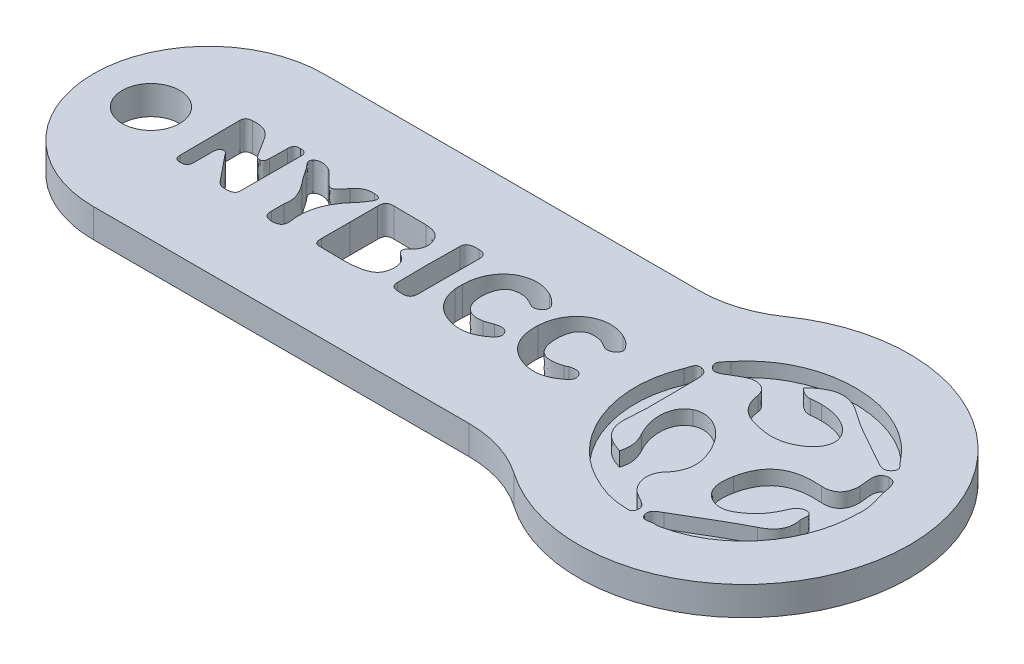
SolidWorks part; units mm, degrees
ref_plane "Plan de face" through (0, 0, 0) normal (0, 0, 1) x (1, 0, 0)
ref_plane "Plan de dessus" through (0, 0, 0) normal (0, 1, 0) x (1, 0, 0)
ref_plane "Plan de droite" through (0, 0, 0) normal (1, 0, 0) x (0, 0, -1)
sketch "Esquisse1" plane through (0, 0, 0) normal (0, 1, 0) x (1, 0, 0)
  line L0 (-14.5, 0) -> (0, 0) construction
  line L1 (-18.5, 8) -> (18.5, 8)
  line L2 (-18.5, 8) -> (-18.5, -8)
  line L3 (-18.5, -8) -> (18.5, -8)
  line L5 (-18.5, 8) -> (18.5, -8) construction
  line L6 (-18.5, -8) -> (18.5, 8) construction
  arc A0 (18.5, -8) -> (18.5, 8) centre (26.7614, 0) ccw
  circle A1 centre (-14.5, 0) radius 2
  point P0 (0, 0)
  dimension "D3" = 23
  dimension "D5" = 4
  dimension "D1" = 37
  dimension "D2" = 16
  dimension "D4" = 4
extrude "Boss.-Extru.1" add sketch "Esquisse1" along normal blind 2
sketch "Esquisse2" plane through (0, 2, 0) normal (0, 1, 0) x (1, 0, 0)
  line L0 (20.6551, -5.913) -> (-11.0872, -5.913)
  line L1 (-11.0872, -5.913) -> (-11.0872, 5.913)
  line L2 (-11.0872, 5.913) -> (20.6551, 5.913)
  line L3 (20.6551, 5.913) -> (20.5787, 5.7726)
  line L7 (18.5, 8) -> (-18.5, 8)
  line L8 (-18.5, 8) -> (-18.5, -8)
  line L9 (-18.5, -8) -> (18.5, -8)
  line L10 (18.5, 8) -> (-18.5, 8)
  line L11 (-18.5, 8) -> (-18.5, -8)
  line L12 (-18.5, -8) -> (18.5, -8)
  arc A2 (20.6551, -5.913) -> (20.6551, 5.913) centre (26.7614, 0) ccw
  arc A3 (20.6551, -5.913) -> (20.6551, 5.913) centre (26.7614, 0) ccw
  arc A4 (18.5, -8) -> (18.5, 8) centre (26.7614, 0) ccw
  arc A5 (18.5, -8) -> (18.5, 8) centre (26.7614, 0) ccw
  spline S0 degree 3 poles (-0.6478, -2.0038) (-0.6441, -1.3402) (-0.6453, -0.6767) (-0.6445, -0.0131) knots 10 10 10 10 11 11 11 11
  spline S1 degree 3 poles (-0.2444, -2.5319) (-0.5915, -2.5436) (-0.6494, -2.2881) (-0.6478, -2.0038) knots 9 9 9 9 10 10 10 10
  spline S2 degree 3 poles (2.6339, -2.4261) (1.6814, -2.6501) (0.7151, -2.4999) (-0.2444, -2.5319) knots 8 8 8 8 9 9 9 9
  spline S3 degree 3 poles (3.5955, -1.6042) (3.4795, -2.1073) (3.0976, -2.3172) (2.6339, -2.4261) knots 7 7 7 7 8 8 8 8
  spline S4 degree 3 poles (3.1404, -0.2543) (3.6591, -0.5766) (3.7194, -1.067) (3.5955, -1.6042) knots 6 6 6 6 7 7 7 7
  spline S5 degree 3 poles (3.0614, 0.4466) (2.7421, 0.169) (2.8091, -0.0484) (3.1404, -0.2543) knots 5 5 5 5 6 6 6 6
  spline S6 degree 3 poles (3.3667, 1.7784) (3.5818, 1.2681) (3.4841, 0.8142) (3.0614, 0.4466) knots 4 4 4 4 5 5 5 5
  spline S7 degree 3 poles (2.1595, 2.4683) (2.6617, 2.4468) (3.1433, 2.3081) (3.3667, 1.7784) knots 3 3 3 3 4 4 4 4
  spline S8 degree 3 poles (-0.0875, 2.4853) (0.6611, 2.4633) (1.4117, 2.5002) (2.1595, 2.4683) knots 2 2 2 2 3 3 3 3
  spline S9 degree 3 poles (-0.6469, 1.9131) (-0.6578, 2.3192) (-0.5122, 2.4979) (-0.0875, 2.4853) knots 1 1 1 1 2 2 2 2
  spline S10 degree 3 poles (-0.6445, -0.0131) (-0.6437, 0.629) (-0.6298, 1.2714) (-0.6469, 1.9131) knots 0 0 0 0 1 1 1 1
  spline S11 degree 3 poles (-6.326, 2.2344) (-6.3313, 1.5279) (-6.3292, 0.8215) (-6.3298, 0.115) knots 18 18 18 18 19 19 19 19
  spline S12 degree 3 poles (-6.7937, 2.7014) (-6.4734, 2.6981) (-6.3236, 2.5559) (-6.326, 2.2344) knots 17 17 17 17 18 18 18 18
  spline S13 degree 3 poles (-7.2477, 2.2297) (-7.2527, 2.5492) (-7.1247, 2.7049) (-6.7937, 2.7014) knots 16 16 16 16 17 17 17 17
  spline S14 degree 3 poles (-7.2678, 1.0107) (-7.2422, 1.4159) (-7.2415, 1.8234) (-7.2477, 2.2297) knots 15 15 15 15 16 16 16 16
  spline S15 degree 3 poles (-7.5105, 0.6021) (-7.2992, 0.6429) (-7.278, 0.8514) (-7.2678, 1.0107) knots 14 14 14 14 15 15 15 15
  spline S16 degree 3 poles (-7.9101, 0.8663) (-7.8168, 0.7208) (-7.7099, 0.5635) (-7.5105, 0.6021) knots 13 13 13 13 14 14 14 14
  spline S17 degree 3 poles (-8.6262, 2.0024) (-8.398, 1.6174) (-8.1518, 1.2431) (-7.9101, 0.8663) knots 12 12 12 12 13 13 13 13
  spline S18 degree 3 poles (-10.1531, 2.7061) (-9.5006, 2.7681) (-8.9761, 2.5926) (-8.6262, 2.0024) knots 11 11 11 11 12 12 12 12
  spline S19 degree 3 poles (-10.6046, 2.2872) (-10.5907, 2.573) (-10.4437, 2.6929) (-10.1531, 2.7061) knots 10 10 10 10 11 11 11 11
  spline S20 degree 3 poles (-10.5829, -1.8867) (-10.591, -0.4954) (-10.5979, 0.8959) (-10.6046, 2.2872) knots 9 9 9 9 10 10 10 10
  spline S21 degree 3 poles (-10.1559, -2.3223) (-10.4501, -2.3155) (-10.5895, -2.1754) (-10.5829, -1.8867) knots 8 8 8 8 9 9 9 9
  spline S22 degree 3 poles (-9.6607, -1.8867) (-9.6658, -2.2196) (-9.8476, -2.3294) (-10.1559, -2.3223) knots 7 7 7 7 8 8 8 8
  spline S23 degree 3 poles (-9.6574, -0.6023) (-9.6581, -1.0305) (-9.6639, -1.4586) (-9.6607, -1.8867) knots 6 6 6 6 7 7 7 7
  spline S24 degree 3 poles (-9.4396, -0.1044) (-9.6359, -0.1895) (-9.657, -0.4031) (-9.6574, -0.6023) knots 5 5 5 5 6 6 6 6
  spline S25 degree 3 poles (-8.9907, -0.371) (-9.1068, -0.2291) (-9.2067, -0.0034) (-9.4396, -0.1044) knots 4 4 4 4 5 5 5 5
  spline S26 degree 3 poles (-7.6174, -2.066) (-8.071, -1.4976) (-8.5298, -0.9334) (-8.9907, -0.371) knots 3 3 3 3 4 4 4 4
  spline S27 degree 3 poles (-6.6227, -2.3125) (-6.978, -2.3961) (-7.3461, -2.4059) (-7.6174, -2.066) knots 2 2 2 2 3 3 3 3
  spline S28 degree 3 poles (-6.3332, -1.619) (-6.3358, -1.8884) (-6.2546, -2.2259) (-6.6227, -2.3125) knots 1 1 1 1 2 2 2 2
  spline S29 degree 3 poles (-6.3298, 0.115) (-6.3304, -0.463) (-6.3278, -1.041) (-6.3332, -1.619) knots 0 0 0 0 1 1 1 1
  spline S30 degree 3 poles (15.134, 1.5867) (14.1247, 1.8204) (13.5732, 1.3125) (13.5613, 0.1569) knots 11 11 11 11 12 12 12 12
  spline S31 degree 3 poles (15.6468, 1.3409) (15.4848, 1.4388) (15.3146, 1.5449) (15.134, 1.5867) knots 10 10 10 10 11 11 11 11
  spline S32 degree 3 poles (16.5098, 1.4875) (16.2919, 1.2335) (15.9824, 1.138) (15.6468, 1.3409) knots 9 9 9 9 10 10 10 10
  spline S33 degree 3 poles (16.3221, 2.2066) (16.5147, 2.0011) (16.7459, 1.7626) (16.5098, 1.4875) knots 8 8 8 8 9 9 9 9
  spline S34 degree 3 poles (15.6943, 2.6388) (15.9312, 2.5316) (16.1453, 2.3955) (16.3221, 2.2066) knots 7 7 7 7 8 8 8 8
  spline S35 degree 3 poles (12.1198, 0.2826) (12.2175, 2.2847) (13.9775, 3.4157) (15.6943, 2.6388) knots 6 6 6 6 7 7 7 7
  spline S36 degree 3 poles (13.463, -2.2907) (12.4307, -1.7591) (12.0672, -0.7993) (12.1198, 0.2826) knots 5 5 5 5 6 6 6 6
  spline S37 degree 3 poles (16.1783, -2.0982) (15.3182, -2.723) (14.3882, -2.7673) (13.463, -2.2907) knots 4 4 4 4 5 5 5 5
  spline S38 degree 3 poles (16.5422, -1.3117) (16.7435, -1.6759) (16.4351, -1.9116) (16.1783, -2.0982) knots 3 3 3 3 4 4 4 4
  spline S39 degree 3 poles (15.6862, -1.1133) (16.0121, -1.0073) (16.3614, -0.9848) (16.5422, -1.3117) knots 2 2 2 2 3 3 3 3
  spline S40 degree 3 poles (15.4506, -1.2123) (15.5311, -1.1849) (15.6054, -1.1395) (15.6862, -1.1133) knots 1 1 1 1 2 2 2 2
  spline S41 degree 3 poles (13.5613, 0.1569) (13.5475, -1.1495) (14.2151, -1.6336) (15.4506, -1.2123) knots 0 0 0 0 1 1 1 1
  spline S42 degree 3 poles (7.034, -0.3815) (7.0099, -0.2138) (7.031, -0.0396) (7.0312, 0.1316) knots 13 13 13 13 14 14 14 14
  spline S43 degree 3 poles (8.5112, -2.4007) (7.6222, -2.0382) (7.1681, -1.3141) (7.034, -0.3815) knots 12 12 12 12 13 13 13 13
  spline S44 degree 3 poles (11.06, -2.1085) (10.272, -2.7073) (9.3984, -2.7625) (8.5112, -2.4007) knots 11 11 11 11 12 12 12 12
  spline S45 degree 3 poles (11.3988, -1.3117) (11.6114, -1.6699) (11.317, -1.9133) (11.06, -2.1085) knots 10 10 10 10 11 11 11 11
  spline S46 degree 3 poles (10.5288, -1.1382) (10.8494, -1.041) (11.2051, -0.9855) (11.3988, -1.3117) knots 9 9 9 9 10 10 10 10
  spline S47 degree 3 poles (9.9235, -1.34) (10.1303, -1.2982) (10.3252, -1.1999) (10.5288, -1.1382) knots 8 8 8 8 9 9 9 9
  spline S48 degree 3 poles (8.5188, -0.6533) (8.7101, -1.2108) (9.2409, -1.4781) (9.9235, -1.34) knots 7 7 7 7 8 8 8 8
  spline S49 degree 3 poles (9.0314, 1.5012) (8.4752, 1.2287) (8.2314, 0.1846) (8.5188, -0.6533) knots 6 6 6 6 7 7 7 7
  spline S50 degree 3 poles (9.4007, 1.5885) (9.2759, 1.5669) (9.1423, 1.5555) (9.0314, 1.5012) knots 5 5 5 5 6 6 6 6
  spline S51 degree 3 poles (10.6171, 1.2922) (10.2401, 1.5152) (9.8484, 1.6661) (9.4007, 1.5885) knots 4 4 4 4 5 5 5 5
  spline S52 degree 3 poles (11.3616, 1.4608) (11.1665, 1.251) (10.9118, 1.1179) (10.6171, 1.2922) knots 3 3 3 3 4 4 4 4
  spline S53 degree 3 poles (11.2404, 2.1354) (11.4173, 1.9545) (11.5948, 1.7118) (11.3616, 1.4608) knots 2 2 2 2 3 3 3 3
  spline S54 degree 3 poles (10.627, 2.5891) (10.8519, 2.4763) (11.0644, 2.3153) (11.2404, 2.1354) knots 1 1 1 1 2 2 2 2
  spline S55 degree 3 poles (7.0312, 0.1316) (7.017, 2.2181) (8.8598, 3.4766) (10.627, 2.5891) knots 0 0 0 0 1 1 1 1
  spline S56 degree 3 poles (20.8247, -2.0529) (20.69, -3.4272) (21.2917, -4.0532) (22.4958, -4.411) knots 13 13 13 13 14 14 14 14
  spline S57 degree 3 poles (20.8707, 2.5877) (20.8518, 1.04) (20.975, -0.5195) (20.8247, -2.0529) knots 12 12 12 12 13 13 13 13
  spline S58 degree 3 poles (20.3589, 3.4373) (20.7757, 3.356) (20.8759, 3.0031) (20.8707, 2.5877) knots 11 11 11 11 12 12 12 12
  spline S59 degree 3 poles (19.7877, 2.7925) (19.904, 3.0638) (19.9018, 3.5264) (20.3589, 3.4373) knots 10 10 10 10 11 11 11 11
  spline S60 degree 3 poles (23.1867, -6.7698) (19.8096, -4.9332) (18.3001, -0.6793) (19.7877, 2.7925) knots 9 9 9 9 10 10 10 10
  spline S61 degree 3 poles (25.9567, -7.6289) (24.9549, -7.6033) (24.0484, -7.2383) (23.1867, -6.7698) knots 8 8 8 8 9 9 9 9
  spline S62 degree 3 poles (26.6612, -7.3752) (26.5599, -7.7864) (26.214, -7.6353) (25.9567, -7.6289) knots 7 7 7 7 8 8 8 8
  spline S63 degree 3 poles (26.268, -6.6952) (26.5299, -6.8467) (26.7435, -7.0408) (26.6612, -7.3752) knots 6 6 6 6 7 7 7 7
  spline S64 degree 3 poles (25.7401, -6.3888) (25.9117, -6.4978) (26.0918, -6.5935) (26.268, -6.6952) knots 5 5 5 5 6 6 6 6
  spline S65 degree 3 poles (25.3508, -4.1307) (24.7364, -4.8112) (24.986, -5.9092) (25.7401, -6.3888) knots 4 4 4 4 5 5 5 5
  spline S66 degree 3 poles (25.5618, -1.0872) (26.0741, -2.135) (26.252, -3.1326) (25.3508, -4.1307) knots 3 3 3 3 4 4 4 4
  spline S67 degree 3 poles (22.5765, 0.6204) (23.5077, 1.0885) (24.8768, 0.3142) (25.5618, -1.0872) knots 2 2 2 2 3 3 3 3
  spline S68 degree 3 poles (22.2705, -2.6617) (21.4852, -1.2334) (21.6533, 0.1562) (22.5765, 0.6204) knots 1 1 1 1 2 2 2 2
  spline S69 degree 3 poles (22.4958, -4.411) (22.6895, -3.7654) (22.5874, -3.2375) (22.2705, -2.6617) knots 0 0 0 0 1 1 1 1
  spline S70 degree 3 poles (34.2908, 1.9196) (34.5116, 1.2692) (34.6572, 0.5833) (34.5723, 0.043) knots 15 15 15 15 16 16 16 16
  spline S71 degree 3 poles (33.4768, 3.345) (34.1825, 3.4033) (34.1107, 2.4507) (34.2908, 1.9196) knots 14 14 14 14 15 15 15 15
  spline S72 degree 3 poles (32.9899, 1.8117) (32.9782, 2.3605) (32.6504, 3.2769) (33.4768, 3.345) knots 13 13 13 13 14 14 14 14
  spline S73 degree 3 poles (31.6503, 0.4778) (32.418, 0.4191) (33.0107, 0.8361) (32.9899, 1.8117) knots 12 12 12 12 13 13 13 13
  spline S74 degree 3 poles (28.0087, -2.0014) (28.3864, -0.1074) (29.5871, 0.6354) (31.6503, 0.4778) knots 11 11 11 11 12 12 12 12
  spline S75 degree 3 poles (28.7232, -4.1459) (27.8705, -3.6814) (27.8418, -2.8385) (28.0087, -2.0014) knots 10 10 10 10 11 11 11 11
  spline S76 degree 3 poles (30.8285, -3.6402) (30.2151, -4.1482) (29.5238, -4.582) (28.7232, -4.1459) knots 9 9 9 9 10 10 10 10
  spline S77 degree 3 poles (31.9149, -2.0477) (31.6643, -2.6604) (31.3386, -3.2179) (30.8285, -3.6402) knots 8 8 8 8 9 9 9 9
  spline S78 degree 3 poles (32.6672, -1.5283) (32.3502, -1.494) (32.0434, -1.7332) (31.9149, -2.0477) knots 7 7 7 7 8 8 8 8
  spline S79 degree 3 poles (32.9603, -2.3153) (32.9084, -2.0339) (33.1548, -1.5813) (32.6672, -1.5283) knots 6 6 6 6 7 7 7 7
  spline S80 degree 3 poles (31.9014, -4.2266) (32.7588, -3.7947) (33.1312, -3.2385) (32.9603, -2.3153) knots 5 5 5 5 6 6 6 6
  spline S81 degree 3 poles (27.7784, -6.5813) (29.1518, -5.7938) (30.49, -4.9378) (31.9014, -4.2266) knots 4 4 4 4 5 5 5 5
  spline S82 degree 3 poles (27.221, -7.3854) (27.066, -6.9234) (27.4568, -6.7657) (27.7784, -6.5813) knots 3 3 3 3 4 4 4 4
  spline S83 degree 3 poles (28.1667, -7.6063) (27.8477, -7.5375) (27.3951, -7.903) (27.221, -7.3854) knots 2 2 2 2 3 3 3 3
  spline S84 degree 3 poles (28.5281, -7.569) (28.4093, -7.5932) (28.2794, -7.6307) (28.1667, -7.6063) knots 1 1 1 1 2 2 2 2
  spline S85 degree 3 poles (34.5723, 0.043) (34.5572, -3.6847) (31.9805, -6.8615) (28.5281, -7.569) knots 0 0 0 0 1 1 1 1
  spline S86 degree 3 poles (-4.0375, -2.0941) (-4.0389, -1.837) (-4.0371, -1.5798) (-4.0366, -1.1939) knots 12 12 12 12 13 13 13 13
  spline S87 degree 3 poles (-3.4486, -2.6866) (-3.8547, -2.6721) (-4.0351, -2.4835) (-4.0375, -2.0941) knots 11 11 11 11 12 12 12 12
  spline S88 degree 3 poles (-2.7742, -2.0038) (-2.7002, -2.4967) (-2.9519, -2.7045) (-3.4486, -2.6866) knots 10 10 10 10 11 11 11 11
  spline S89 degree 3 poles (-1.6158, 1.3812) (-2.4983, 0.4205) (-2.9748, -0.6693) (-2.7742, -2.0038) knots 9 9 9 9 10 10 10 10
  spline S90 degree 3 poles (-1.2023, 1.9516) (-1.3309, 1.7551) (-1.4579, 1.5531) (-1.6158, 1.3812) knots 8 8 8 8 9 9 9 9
  spline S91 degree 3 poles (-1.5107, 2.5549) (-1.0074, 2.5231) (-0.9576, 2.3253) (-1.2023, 1.9516) knots 7 7 7 7 8 8 8 8
  spline S92 degree 3 poles (-2.6553, 2.0123) (-2.3469, 2.4021) (-2.0134, 2.5867) (-1.5107, 2.5549) knots 6 6 6 6 7 7 7 7
  spline S93 degree 3 poles (-4.0605, 1.947) (-3.3405, 1.182) (-3.3258, 1.1647) (-2.6553, 2.0123) knots 5 5 5 5 6 6 6 6
  spline S94 degree 3 poles (-4.6349, 2.4518) (-4.4141, 2.3416) (-4.2354, 2.1329) (-4.0605, 1.947) knots 4 4 4 4 5 5 5 5
  spline S95 degree 3 poles (-5.6628, 2.4363) (-5.4111, 2.6916) (-4.9649, 2.6164) (-4.6349, 2.4518) knots 3 3 3 3 4 4 4 4
  spline S96 degree 3 poles (-5.3839, 1.679) (-5.5353, 1.9141) (-5.9259, 2.1694) (-5.6628, 2.4363) knots 2 2 2 2 3 3 3 3
  spline S97 degree 3 poles (-4.6793, 0.6846) (-4.935, 0.9994) (-5.164, 1.3377) (-5.3839, 1.679) knots 1 1 1 1 2 2 2 2
  spline S98 degree 3 poles (-4.0366, -1.1939) (-3.8891, -0.5375) (-4.2008, 0.0951) (-4.6793, 0.6846) knots 0 0 0 0 1 1 1 1
  spline S99 degree 3 poles (28.4489, 6.1036) (27.188, 7.04) (26.1934, 6.8331) (25.1006, 5.7726) knots 13 13 13 13 14 14 14 14
  spline S100 degree 3 poles (32.2257, 3.8741) (30.9697, 4.6247) (29.6158, 5.2371) (28.4489, 6.1036) knots 12 12 12 12 13 13 13 13
  spline S101 degree 3 poles (33.1947, 3.8749) (32.8996, 3.5244) (32.5762, 3.6646) (32.2257, 3.8741) knots 11 11 11 11 12 12 12 12
  spline S102 degree 3 poles (32.9181, 4.6879) (33.0852, 4.4632) (33.51, 4.2491) (33.1947, 3.8749) knots 10 10 10 10 11 11 11 11
  spline S103 degree 3 poles (21.0052, 4.8289) (23.9283, 8.5635) (30.0923, 8.4884) (32.9181, 4.6879) knots 9 9 9 9 10 10 10 10
  spline S104 degree 3 poles (20.6512, 3.9116) (20.3706, 4.3111) (20.8091, 4.5784) (21.0052, 4.8289) knots 8 8 8 8 9 9 9 9
  spline S105 degree 3 poles (21.7112, 3.951) (21.3602, 3.7373) (20.9758, 3.4496) (20.6512, 3.9116) knots 7 7 7 7 8 8 8 8
  spline S106 degree 3 poles (22.4531, 4.3729) (22.1989, 4.2458) (21.9541, 4.099) (21.7112, 3.951) knots 6 6 6 6 7 7 7 7
  spline S107 degree 3 poles (23.9755, 3.7431) (23.8907, 4.348) (23.204, 4.7486) (22.4531, 4.3729) knots 5 5 5 5 6 6 6 6
  spline S108 degree 3 poles (26.5035, 1.7576) (25.3358, 1.9291) (24.1957, 2.1695) (23.9755, 3.7431) knots 4 4 4 4 5 5 5 5
  spline S109 degree 3 poles (29.457, 3.5205) (29.4094, 2.5046) (27.9199, 1.5498) (26.5035, 1.7576) knots 3 3 3 3 4 4 4 4
  spline S110 degree 3 poles (26.7445, 5.4024) (28.3033, 5.391) (29.5054, 4.5538) (29.457, 3.5205) knots 2 2 2 2 3 3 3 3
  spline S111 degree 3 poles (26.0136, 5.3603) (26.2569, 5.3802) (26.5009, 5.4042) (26.7445, 5.4024) knots 1 1 1 1 2 2 2 2
  spline S112 degree 3 poles (25.1006, 5.7726) (25.3972, 5.4799) (25.6664, 5.3319) (26.0136, 5.3603) knots 0 0 0 0 1 1 1 1
  spline S113 degree 3 poles (6.0618, 2.2443) (6.0551, 1.5401) (6.0584, 0.8358) (6.0578, 0.1316) knots 6 6 6 6 7 7 7 7
  spline S114 degree 3 poles (5.4775, 2.8223) (5.8787, 2.8327) (6.0656, 2.6459) (6.0618, 2.2443) knots 5 5 5 5 6 6 6 6
  spline S115 degree 3 poles (4.644, 2.3472) (4.6569, 2.8368) (5.1086, 2.8127) (5.4775, 2.8223) knots 4 4 4 4 5 5 5 5
  spline S116 degree 3 poles (4.6408, -2.0038) (4.607, -0.5541) (4.6057, 0.8976) (4.644, 2.3472) knots 3 3 3 3 4 4 4 4
  spline S117 degree 3 poles (5.5027, -2.5204) (5.0987, -2.5151) (4.653, -2.5272) (4.6408, -2.0038) knots 2 2 2 2 3 3 3 3
  spline S118 degree 3 poles (6.0561, -1.9172) (6.0567, -2.2902) (5.9381, -2.526) (5.5027, -2.5204) knots 1 1 1 1 2 2 2 2
  spline S119 degree 3 poles (6.0578, 0.1316) (6.0573, -0.5513) (6.055, -1.2343) (6.0561, -1.9172) knots 0 0 0 0 1 1 1 1
  dimension "D1" = 3
  dimension "D2" = 0
sketch "Esquisse3" plane through (0, 2, 0) normal (0, 1, 0) x (1, 0, 0)
  line L0 (-18.5, -8) -> (18.5, -8) construction
  line L1 (18.5, 8) -> (-18.5, 8) construction
  line L2 (-18.5, 8) -> (-18.5, -8) construction
  line L3 (-18.5, -8) -> (18.5, -8)
  line L4 (18.5, 8) -> (-18.5, 8)
  line L5 (-18.5, 8) -> (-18.5, -8)
  line L6 (20.6551, -5.913) -> (-11.0872, -5.913) construction
  line L7 (-11.0872, -5.913) -> (-11.0872, 5.913) construction
  line L8 (-11.0872, 5.913) -> (20.6551, 5.913) construction
  line L9 (20.6551, -5.913) -> (-11.0872, -5.913)
  line L10 (-11.0872, -5.913) -> (-11.0872, 5.913)
  line L11 (-11.0872, 5.913) -> (20.6551, 5.913)
  arc A0 (18.5, -8) -> (18.5, 8) centre (26.7614, 0) ccw construction
  arc A1 (18.5, -8) -> (18.5, 8) centre (26.7614, 0) ccw
  arc A2 (20.6551, -5.913) -> (20.6551, 5.913) centre (26.7614, 0) ccw construction
  arc A3 (20.6551, -5.913) -> (20.6551, 5.913) centre (26.7614, 0) ccw
  circle A4 centre (-14.5, 0) radius 2 construction
  circle A5 centre (-14.5, 0) radius 2
sketch "Esquisse4" plane through (0, 2, 0) normal (0, 1, 0) x (1, 0, 0)
  line L0 (20.6551, 5.913) -> (20.5787, 5.7726) construction
  line L7 (20.6551, 5.913) -> (20.5787, 5.7726)
  spline S0 degree 3 poles (-988.6364, -156.5278) (987.1828, 15.4399) (-988.3584, -17.0259) (987.0045, 156.5819) knots -42.156378 -42.156378 -42.156378 -42.156378 63.578843 63.578843 63.578843 63.578843 only from (-0.6478, -2.0038) to (-0.6445, -0.0131) construction
  spline S1 degree 3 poles (998.9683, -27.814) (-1000.7869, -43.7538) (999.5085, 44.8287) (-1000.2647, 29.0633) knots -28.01613 -28.01613 -28.01613 -28.01613 28.610346 28.610346 28.610346 28.610346 only from (-0.6445, -0.0131) to (-0.6469, 1.9131) construction
  spline S2 degree 3 poles (-806.3377, -590.4224) (881.935, 349.9228) (-947.6891, -158.8633) (999.6546, 24.973) knots -19.095692 -19.095692 -19.095692 -19.095692 19.93203 19.93203 19.93203 19.93203 only from (-0.6469, 1.9131) to (-0.0875, 2.4853) construction
  spline S3 degree 3 poles (-5.6723, 1002.4697) (-52.037, -997.9234) (54.0549, 1002.8855) (7.2197, -997.5168) knots -17.384502 -17.384502 -17.384502 -17.384502 22.307886 22.307886 22.307886 22.307886 only from (-0.0875, 2.4853) to (2.1595, 2.4683) construction
  spline S4 degree 3 poles (673.4526, 743.6589) (-679.078, -755.5216) (663.7455, 775.9327) (-613.6237, -785.1772) knots -11.375763 -11.375763 -11.375763 -11.375763 16.803532 16.803532 16.803532 16.803532 only from (2.1595, 2.4683) to (3.3667, 1.7784) construction
  spline S5 degree 3 poles (-587.2716, -805.1573) (-148.2054, 805.2207) (588.7087, -710.7698) (-808.9164, 584.1264) knots -28.547334 -28.547334 -28.547334 -28.547334 29.703561 29.703561 29.703561 29.703561 only from (3.3667, 1.7784) to (3.0614, 0.4466) construction
  spline S6 degree 3 poles (954.8081, 307.3287) (-985.562, -347.9861) (973.0885, 409.0271) (-860.9773, -503.5381) knots -12.018303 -12.018303 -12.018303 -12.018303 27.813032 27.813032 27.813032 27.813032 only from (3.0614, 0.4466) to (3.1404, -0.2543) construction
  spline S7 degree 3 poles (-925.837, -370.3897) (942.0359, 411.4876) (-930.5378, -430.2075) (917.0272, 405.3868) knots -7.406116 -7.406116 -7.406116 -7.406116 22.66661 22.66661 22.66661 22.66661 only from (3.1404, -0.2543) to (3.5955, -1.6042) construction
  spline S8 degree 3 poles (-670.3816, 737.1466) (709.5487, -735.2893) (-709.848, 726.7854) (686.6085, -731.9215) knots -7.128626 -7.128626 -7.128626 -7.128626 24.107352 24.107352 24.107352 24.107352 only from (3.5955, -1.6042) to (2.6339, -2.4261) construction
  spline S9 degree 3 poles (-1.3954, 997.5644) (49.6027, -1003.949) (-48.2188, 998.8305) (2.8476, -1002.5252) knots -3.490216 -3.490216 -3.490216 -3.490216 20.834721 20.834721 20.834721 20.834721 only from (2.6339, -2.4261) to (-0.2444, -2.5319) construction
  spline S10 degree 3 poles (709.1918, 702.2371) (-704.6122, -729.3467) (696.5433, 732.4618) (-690.1218, -726.3134) knots -4.311026 -4.311026 -4.311026 -4.311026 24.68846 24.68846 24.68846 24.68846 only from (-0.2444, -2.5319) to (-0.6478, -2.0038) construction
  spline S11 degree 3 poles (77.2752, -996.4806) (274.7762, 726.1333) (-598.1401, -348.7164) (1002.8087, -146.0471) knots -5.22656 -5.22656 -5.22656 -5.22656 29.924053 29.924053 29.924053 29.924053 only from (15.134, 1.5867) to (13.5613, 0.1569) construction
  spline S12 degree 3 poles (951.6619, 346.5188) (-635.4613, 133.2102) (336.241, -584.3672) (57.8715, 997.8829) knots -15.670122 -15.670122 -15.670122 -15.670122 16.612834 16.612834 16.612834 16.612834 only from (13.5613, 0.1569) to (15.4506, -1.2123) construction
  spline S13 degree 3 poles (-312.5767, 943.4558) (334.4675, -950.078) (-303.2207, 947.7902) (343.3536, -945.9047) knots -27.953246 -27.953246 -27.953246 -27.953246 30.921786 30.921786 30.921786 30.921786 only from (15.4506, -1.2123) to (15.6862, -1.1133) construction
  spline S14 degree 3 poles (629.3392, 788.4617) (-592.9202, -814.6705) (600.3995, 828.8234) (-527.5758, -840.2992) knots -12.722398 -12.722398 -12.722398 -12.722398 16.387117 16.387117 16.387117 16.387117 only from (15.6862, -1.1133) to (16.5422, -1.3117) construction
  spline S15 degree 3 poles (-968.5973, 170.4413) (1016.2092, -148.9038) (-986.1997, 128.5795) (1008.4751, -125.9023) knots -8.191963 -8.191963 -8.191963 -8.191963 16.038152 16.038152 16.038152 16.038152 only from (16.5422, -1.3117) to (16.1783, -2.0982) construction
  spline S16 degree 3 poles (-413.0221, 901.1107) (649.4811, -798.7358) (-827.89, 497.4191) (1008.0457, 101.5793) knots -13.642897 -13.642897 -13.642897 -13.642897 29.172404 29.172404 29.172404 29.172404 only from (16.1783, -2.0982) to (13.463, -2.2907) construction
  spline S17 degree 3 poles (753.6553, 670.1039) (-691.3994, -782.2796) (648.2073, 850.2029) (-518.9928, -847.0113) knots -6.861822 -6.861822 -6.861822 -6.861822 20.712814 20.712814 20.712814 20.712814 only from (13.463, -2.2907) to (12.1198, 0.2826) construction
  spline S18 degree 3 poles (983.8627, 236.3137) (-894.6339, -432.4693) (816.8689, 609.7286) (-644.5915, -748.3538) knots -1.42749 -1.42749 -1.42749 -1.42749 14.40084 14.40084 14.40084 14.40084 only from (12.1198, 0.2826) to (15.6943, 2.6388) construction
  spline S19 degree 3 poles (497.6319, 878.8442) (-512.7977, -858.361) (550.6357, 859.2915) (-493.7576, -857.91) knots -27.417212 -27.417212 -27.417212 -27.417212 38.78624 38.78624 38.78624 38.78624 only from (15.6943, 2.6388) to (16.3221, 2.2066) construction
  spline S20 degree 3 poles (1016.3205, 1.5475) (-993.2394, 2.8192) (1025.7844, 12.042) (-983.0278, -28.8534) knots -4.504445 -4.504445 -4.504445 -4.504445 20.654847 20.654847 20.654847 20.654847 only from (16.3221, 2.2066) to (16.5098, 1.4875) construction
  spline S21 degree 3 poles (-549.5158, -822.8998) (492.9297, 901.9294) (-364.3464, -942.0156) (298.2154, 960.5824) knots -10.368356 -10.368356 -10.368356 -10.368356 27.013914 27.013914 27.013914 27.013914 only from (16.5098, 1.4875) to (15.6468, 1.3409) construction
  spline S22 degree 3 poles (44.1669, 1000.9336) (-6.941, -1007.214) (47.835, 1009.487) (-42.0952, -996.7713) knots -13.923169 -13.923169 -13.923169 -13.923169 34.138233 34.138233 34.138233 34.138233 only from (15.6468, 1.3409) to (15.134, 1.5867) construction
  spline S23 degree 3 poles (990.6662, 77.5648) (-1003.4013, 25.6067) (990.7593, -26.3513) (-1003.3786, -78.3094) knots -44.663535 -44.663535 -44.663535 -44.663535 45.225593 45.225593 45.225593 45.225593 only from (-6.3298, 0.115) to (-6.3332, -1.619) construction
  spline S24 degree 3 poles (989.2196, 96.5132) (-1001.8672, 35.4149) (989.1774, -34.094) (-1001.7881, -94.9232) knots -27.444711 -27.444711 -27.444711 -27.444711 64.89824 64.89824 64.89824 64.89824 only from (-6.326, 2.2344) to (-6.3298, 0.115) construction
  spline S25 degree 3 poles (-836.2326, 561.2977) (474.0948, -727.7598) (-215.9337, 879.5735) (-3.6561, -997.7607) knots -10.970401 -10.970401 -10.970401 -10.970401 43.07894 43.07894 43.07894 43.07894 only from (-6.7937, 2.7014) to (-6.326, 2.2344) construction
  spline S26 degree 3 poles (-913.0808, -421.4039) (950.0679, 142.5938) (-989.151, 53.0134) (978.2504, -169.5259) knots -9.532921 -9.532921 -9.532921 -9.532921 38.386034 38.386034 38.386034 38.386034 only from (-7.2477, 2.2297) to (-6.7937, 2.7014) construction
  spline S27 degree 3 poles (-999.1667, 128.0396) (985.1932, -190.9992) (-998.8826, 203.0445) (982.1816, -142.7251) knots -21.670153 -21.670153 -21.670153 -21.670153 54.412041 54.412041 54.412041 54.412041 only from (-7.2678, 1.0107) to (-7.2477, 2.2297) construction
  spline S28 degree 3 poles (-668.8844, 750.6341) (639.1416, -770.9194) (-639.3836, 784.7924) (611.4362, -784.5958) knots -0.397535 -0.397535 -0.397535 -0.397535 30.179574 30.179574 30.179574 30.179574 only from (-7.5105, 0.6021) to (-7.2678, 1.0107) construction
  spline S29 degree 3 poles (-356.6983, -936.3343) (343.2701, 944.3332) (-367.6776, -939.2522) (366.7001, 927.9281) knots -3.513886 -3.513886 -3.513886 -3.513886 29.567438 29.567438 29.567438 29.567438 only from (-7.9101, 0.8663) to (-7.5105, 0.6021) construction
  spline S30 degree 3 poles (829.5855, 547.3472) (-878.5795, -494.1367) (862.563, 496.1606) (-845.9596, -544.7127) knots -20.996165 -20.996165 -20.996165 -20.996165 46.603168 46.603168 46.603168 46.603168 only from (-8.6262, 2.0024) to (-7.9101, 0.8663) construction
  spline S31 degree 3 poles (139.6162, 991.4266) (-271.5087, -1005.6616) (283.374, 998.9785) (-283.9527, -959.333) knots -8.202833 -8.202833 -8.202833 -8.202833 27.34985 27.34985 27.34985 27.34985 only from (-10.1531, 2.7061) to (-8.6262, 2.0024) construction
  spline S32 degree 3 poles (69.505, -994.4985) (45.6843, 968.6223) (-259.4949, -917.538) (503.8031, 860.5068) knots -12.921906 -12.921906 -12.921906 -12.921906 37.27285 37.27285 37.27285 37.27285 only from (-10.6046, 2.2872) to (-10.1531, 2.7061) construction
  spline S33 degree 3 poles (883.7826, -449.2233) (-901.1007, -62.1587) (878.506, 65.9086) (-900.8428, 457.7759) knots -82.945956 -82.945956 -82.945956 -82.945956 103.036068 103.036068 103.036068 103.036068 only from (-10.5829, -1.8867) to (-10.6046, 2.2872) construction
  spline S34 degree 3 poles (974.6124, -176.1925) (-526.4423, 478.1203) (128.9609, -752.9914) (148.1443, 985.4217) knots -27.072413 -27.072413 -27.072413 -27.072413 40.976976 40.976976 40.976976 40.976976 only from (-10.1559, -2.3223) to (-10.5829, -1.8867) construction
  spline S35 degree 3 poles (-486.5605, 877.0701) (458.9451, -914.0132) (-433.3075, 932.6757) (313.8287, -948.3716) knots -11.193802 -11.193802 -11.193802 -11.193802 29.899117 29.899117 29.899117 29.899117 only from (-9.6607, -1.8867) to (-10.1559, -2.3223) construction
  spline S36 degree 3 poles (-1007.9069, 58.5336) (989.028, 10.4052) (-1008.3645, -12.7236) (988.6401, -60.0899) knots -35.027915 -35.027915 -35.027915 -35.027915 47.746664 47.746664 47.746664 47.746664 only from (-9.6574, -0.6023) to (-9.6607, -1.8867) construction
  spline S37 degree 3 poles (743.2511, -658.4775) (-753.2247, 680.9979) (724.5239, -692.6213) (-734.4078, 688.3969) knots -10.827655 -10.827655 -10.827655 -10.827655 22.883053 22.883053 22.883053 22.883053 only from (-9.4396, -0.1044) to (-9.6574, -0.6023) construction
  spline S38 degree 3 poles (332.3164, 939.5804) (-348.7005, -946.9214) (334.9496, 944.7424) (-363.521, -935.3028) knots -9.004552 -9.004552 -9.004552 -9.004552 17.390522 17.390522 17.390522 17.390522 only from (-8.9907, -0.371) to (-9.4396, -0.1044) construction
  spline S39 degree 3 poles (-713.135, -710.7581) (811.6493, 568.6038) (-832.4972, -565.7972) (695.7912, 709.0493) knots -58.876456 -58.876456 -58.876456 -58.876456 68.312933 68.312933 68.312933 68.312933 only from (-7.6174, -2.066) to (-8.9907, -0.371) construction
  spline S40 degree 3 poles (-388.2294, -926.6362) (379.6169, 934.5082) (-375.8428, -945.2003) (325.7642, 940.7118) knots -13.259705 -13.259705 -13.259705 -13.259705 16.823069 16.823069 16.823069 16.823069 only from (-6.6227, -2.3125) to (-7.6174, -2.066) construction
  spline S41 degree 3 poles (852.5834, -513.7346) (-867.9162, 519.8342) (857.4376, -519.6777) (-871.7859, 499.1657) knots -10.568291 -10.568291 -10.568291 -10.568291 12.91224 12.91224 12.91224 12.91224 only from (-6.3332, -1.619) to (-6.6227, -2.3125) construction
  spline S42 degree 3 poles (-976.8766, 151.3618) (1013.8845, -130.1185) (-993.762, 110.4143) (1005.3355, -108.8521) knots -1.305842 -1.305842 -1.305842 -1.305842 23.194195 23.194195 23.194195 23.194195 only from (11.3988, -1.3117) to (11.06, -2.1085) construction
  spline S43 degree 3 poles (528.9071, 854.0125) (-508.5154, -871.207) (512.7016, 878.2898) (-457.6097, -884.4824) knots -4.744692 -4.744692 -4.744692 -4.744692 22.646764 22.646764 22.646764 22.646764 only from (10.5288, -1.1382) to (11.3988, -1.3117) construction
  spline S44 degree 3 poles (-218.5156, 972.2179) (222.1143, -981.2043) (-202.0747, 978.6309) (240.7218, -974.2783) knots -13.30674 -13.30674 -13.30674 -13.30674 30.517685 30.517685 30.517685 30.517685 only from (9.9235, -1.34) to (10.5288, -1.1382) construction
  spline S45 degree 3 poles (986.796, -207.9143) (-883.1681, 409.0561) (781.2194, -605.105) (-607.2737, 785.4635) knots -8.759998 -8.759998 -8.759998 -8.759998 23.985289 23.985289 23.985289 23.985289 only from (8.5188, -0.6533) to (9.9235, -1.34) construction
  spline S46 degree 3 poles (-72.5741, -995.1618) (183.5921, 1009.3755) (-259.8817, -987.932) (368.6327, 932.2462) knots -3.358825 -3.358825 -3.358825 -3.358825 16.723058 16.723058 16.723058 16.723058 only from (9.0314, 1.5012) to (8.5188, -0.6533) construction
  spline S47 degree 3 poles (-496.2342, 864.3353) (525.1624, -860.6724) (-503.936, 865.3035) (507.1121, -865.6245) knots -20.101958 -20.101958 -20.101958 -20.101958 30.530343 30.530343 30.530343 30.530343 only from (9.4007, 1.5885) to (9.0314, 1.5012) construction
  spline S48 degree 3 poles (294.1455, 960.256) (-241.6583, -977.8855) (261.0615, 980.5187) (-263.3617, -960.4783) knots -14.845555 -14.845555 -14.845555 -14.845555 21.93996 21.93996 21.93996 21.93996 only from (10.6171, 1.2922) to (9.4007, 1.5885) construction
  spline S49 degree 3 poles (-119.6518, -989.9189) (117.7344, 1011.2046) (-59.5184, -1010.4126) (37.2145, 1000.9261) knots -13.658737 -13.658737 -13.658737 -13.658737 19.034029 19.034029 19.034029 19.034029 only from (11.3616, 1.4608) to (10.6171, 1.2922) construction
  spline S50 degree 3 poles (999.0738, -153.3766) (-988.735, 145.5198) (1013.8935, -119.3115) (-984.5443, 91.7503) knots -11.421185 -11.421185 -11.421185 -11.421185 15.459892 15.459892 15.459892 15.459892 only from (11.2404, 2.1354) to (11.3616, 1.4608) construction
  spline S51 degree 3 poles (560.3314, -832.7692) (-616.6942, 811.7936) (694.6126, -761.4615) (-705.1624, 699.8076) knots -28.164161 -28.164161 -28.164161 -28.164161 31.711383 31.711383 31.711383 31.711383 only from (10.627, 2.5891) to (11.2404, 2.1354) construction
  spline S52 degree 3 poles (962.6005, 294.8883) (-875.5939, -483.3795) (782.0367, 649.7362) (-617.9537, -775.1371) knots -7.053117 -7.053117 -7.053117 -7.053117 7.970328 7.970328 7.970328 7.970328 only from (7.0312, 0.1316) to (10.627, 2.5891) construction
  spline S53 degree 3 poles (998.7957, 127.7099) (-985.4175, -144.7336) (999.4735, 144.6596) (-984.7492, -127.7376) knots -10.966887 -10.966887 -10.966887 -10.966887 38.335229 38.335229 38.335229 38.335229 only from (7.034, -0.3815) to (7.0312, 0.1316) construction
  spline S54 degree 3 poles (705.3263, 714.8491) (-672.2152, -838.6363) (627.5335, 904.4192) (-499.4443, -862.6252) knots -2.791909 -2.791909 -2.791909 -2.791909 32.623759 32.623759 32.623759 32.623759 only from (8.5112, -2.4007) to (7.034, -0.3815) construction
  spline S55 degree 3 poles (-305.9929, 946.2989) (478.753, -993.3361) (-603.5234, 936.3711) (701.3557, -723.4689) knots -4.894252 -4.894252 -4.894252 -4.894252 34.028566 34.028566 34.028566 34.028566 only from (11.06, -2.1085) to (8.5112, -2.4007) construction
  spline S86 degree 3 poles (-998.0966, 110.9813) (967.8296, 21.1404) (-963.8369, -146.3884) (959.1366, 275.7721) knots -3.460961 -3.460961 -3.460961 -3.460961 14.398386 14.398386 14.398386 14.398386 only from (-4.0605, 1.947) to (-2.6553, 2.0123) construction
  spline S87 degree 3 poles (-330.7575, -942.8753) (300.5, 964.7639) (-300.9362, -963.3534) (298.9036, 954.9468) knots -15.082333 -15.082333 -15.082333 -15.082333 24.760928 24.760928 24.760928 24.760928 only from (-4.6349, 2.4518) to (-4.0605, 1.947) construction
  spline S88 degree 3 poles (730.612, -674.2454) (-792.1417, 645.4043) (815.6522, -598.5669) (-838.9668, 553.6888) knots -9.792495 -9.792495 -9.792495 -9.792495 17.609969 17.609969 17.609969 17.609969 only from (-5.6628, 2.4363) to (-4.6349, 2.4518) construction
  spline S89 degree 3 poles (-1005.3483, 9.9803) (1003.2554, -12.5588) (-1014.3522, 12.4138) (994.3191, 5.4319) knots -8.139428 -8.139428 -8.139428 -8.139428 12.675321 12.675321 12.675321 12.675321 only from (-5.3839, 1.679) to (-5.6628, 2.4363) construction
  spline S90 degree 3 poles (684.886, 724.9073) (-659.1154, -774.1783) (639.8692, 785.8224) (-671.8478, -743.851) knots -31.116553 -31.116553 -31.116553 -31.116553 35.740281 35.740281 35.740281 35.740281 only from (-4.6793, 0.6846) to (-5.3839, 1.679) construction
  spline S91 degree 3 poles (-1003.998, 7.5465) (1027.4399, -61.688) (-1038.4293, 89.9639) (992.1192, -79.2015) knots -13.62104 -13.62104 -13.62104 -13.62104 16.760514 16.760514 16.760514 16.760514 only from (-4.0366, -1.1939) to (-4.6793, 0.6846) construction
  spline S92 degree 3 poles (35.5813, -1001.3082) (-40.9763, 977.2472) (30.3374, -981.8161) (-35.9644, 998.2859) knots -7.697905 -7.697905 -7.697905 -7.697905 31.705642 31.705642 31.705642 31.705642 only from (-4.0375, -2.0941) to (-4.0366, -1.1939) construction
  spline S93 degree 3 poles (995.0972, -56.5966) (-846.6338, 261.4975) (659.4223, -540.3362) (-463.6009, 886.0417) knots -12.326077 -12.326077 -12.326077 -12.326077 37.811125 37.811125 37.811125 37.811125 only from (-3.4486, -2.6866) to (-4.0375, -2.0941) construction
  spline S94 degree 3 poles (-776.0289, 632.0912) (885.6885, -678.1019) (-941.2722, 658.9145) (832.798, -551.0364) knots -7.8277 -7.8277 -7.8277 -7.8277 36.584069 36.584069 36.584069 36.584069 only from (-2.7742, -2.0038) to (-3.4486, -2.6866) construction
  spline S95 degree 3 poles (-879.7301, 479.8305) (985.0011, -401.3615) (-983.6847, 393.8198) (907.2553, -416.514) knots -7.694483 -7.694483 -7.694483 -7.694483 22.804471 22.804471 22.804471 22.804471 only from (-1.6158, 1.3812) to (-2.7742, -2.0038) construction
  spline S96 degree 3 poles (677.4135, -732.5417) (-668.6702, 755.2428) (669.1077, -748.6864) (-688.672, 727.9831) knots -19.404424 -19.404424 -19.404424 -19.404424 35.616796 35.616796 35.616796 35.616796 only from (-1.2023, 1.9516) to (-1.6158, 1.3812) construction
  spline S97 degree 3 poles (-997.9888, -81.2874) (1033.1788, 20.045) (-1027.0297, 109.6042) (945.4499, -320.2944) knots -8.833935 -8.833935 -8.833935 -8.833935 28.267918 28.267918 28.267918 28.267918 only from (-1.5107, 2.5549) to (-1.2023, 1.9516) construction
  spline S98 degree 3 poles (-988.4466, -165.9607) (953.2825, -10.6556) (-952.5304, 157.4031) (963.1996, -260.697) knots -13.052212 -13.052212 -13.052212 -13.052212 24.574585 24.574585 24.574585 24.574585 only from (-2.6553, 2.0123) to (-1.5107, 2.5549) construction
  spline S99 degree 3 poles (1003.235, 77.3765) (-991.1838, 40.4576) (1003.2795, -39.0706) (-991.0605, -75.6894) knots -34.567291 -34.567291 -34.567291 -34.567291 47.999861 47.999861 47.999861 47.999861 only from (6.0618, 2.2443) to (6.0578, 0.1316) construction
  spline S100 degree 3 poles (-990.4073, 84.1389) (1002.7863, 73.2844) (-990.6738, -74.2368) (1002.5246, -85.8329) knots -57.769801 -57.769801 -57.769801 -57.769801 58.453633 58.453633 58.453633 58.453633 only from (6.0578, 0.1316) to (6.0561, -1.9172) construction
  spline S101 degree 3 poles (923.493, -399.7984) (-899.7026, 464.6297) (895.1424, -498.4775) (-862.3284, 494.2933) knots -16.313654 -16.313654 -16.313654 -16.313654 16.802019 16.802019 16.802019 16.802019 only from (6.0561, -1.9172) to (5.5027, -2.5204) construction
  spline S102 degree 3 poles (-644.114, -762.7817) (669.2657, 760.7377) (-654.5277, -768.997) (643.3859, 767.4031) knots -9.086885 -9.086885 -9.086885 -9.086885 13.196899 13.196899 13.196899 13.196899 only from (5.5027, -2.5204) to (4.6408, -2.0038) construction
  spline S103 degree 3 poles (-893.2004, 438.3147) (968.2876, -668.1823) (-982.0484, 540.1623) (983.2506, -203.3467) knots -52.387966 -52.387966 -52.387966 -52.387966 50.593508 50.593508 50.593508 50.593508 only from (4.6408, -2.0038) to (4.644, 2.3472) construction
  spline S104 degree 3 poles (678.4764, -736.5364) (-691.0271, 735.7302) (708.2447, -724.0266) (-687.2764, 723.9834) knots -6.114075 -6.114075 -6.114075 -6.114075 15.899571 15.899571 15.899571 15.899571 only from (4.644, 2.3472) to (5.4775, 2.8223) construction
  spline S105 degree 3 poles (-991.0877, -79.9856) (713.0647, -216.2778) (-399.1903, 579.1364) (97.6192, -993.5439) knots -22.340246 -22.340246 -22.340246 -22.340246 34.868615 34.868615 34.868615 34.868615 only from (5.4775, 2.8223) to (6.0618, 2.2443) construction
  spline S120 degree 3 poles (-0.6478, -2.0038) (-0.6441, -1.3402) (-0.6453, -0.6767) (-0.6445, -0.0131) knots 10 10 10 10 11 11 11 11
  spline S121 degree 3 poles (-0.6445, -0.0131) (-0.6437, 0.629) (-0.6298, 1.2714) (-0.6469, 1.9131) knots 0 0 0 0 1 1 1 1
  spline S122 degree 3 poles (-0.6469, 1.9131) (-0.6578, 2.3192) (-0.5122, 2.4979) (-0.0875, 2.4853) knots 1 1 1 1 2 2 2 2
  spline S123 degree 3 poles (-0.0875, 2.4853) (0.6611, 2.4633) (1.4117, 2.5002) (2.1595, 2.4683) knots 2 2 2 2 3 3 3 3
  spline S124 degree 3 poles (2.1595, 2.4683) (2.6617, 2.4468) (3.1433, 2.3081) (3.3667, 1.7784) knots 3 3 3 3 4 4 4 4
  spline S125 degree 3 poles (3.3667, 1.7784) (3.5818, 1.2681) (3.4841, 0.8142) (3.0614, 0.4466) knots 4 4 4 4 5 5 5 5
  spline S126 degree 3 poles (3.0614, 0.4466) (2.7421, 0.169) (2.8091, -0.0484) (3.1404, -0.2543) knots 5 5 5 5 6 6 6 6
  spline S127 degree 3 poles (3.1404, -0.2543) (3.6591, -0.5766) (3.7194, -1.067) (3.5955, -1.6042) knots 6 6 6 6 7 7 7 7
  spline S128 degree 3 poles (3.5955, -1.6042) (3.4795, -2.1073) (3.0976, -2.3172) (2.6339, -2.4261) knots 7 7 7 7 8 8 8 8
  spline S129 degree 3 poles (2.6339, -2.4261) (1.6814, -2.6501) (0.7151, -2.4999) (-0.2444, -2.5319) knots 8 8 8 8 9 9 9 9
  spline S130 degree 3 poles (-0.2444, -2.5319) (-0.5915, -2.5436) (-0.6494, -2.2881) (-0.6478, -2.0038) knots 9 9 9 9 10 10 10 10
  spline S131 degree 3 poles (15.134, 1.5867) (14.1247, 1.8204) (13.5732, 1.3125) (13.5613, 0.1569) knots 11 11 11 11 12 12 12 12
  spline S132 degree 3 poles (13.5613, 0.1569) (13.5475, -1.1495) (14.2151, -1.6336) (15.4506, -1.2123) knots 0 0 0 0 1 1 1 1
  spline S133 degree 3 poles (15.4506, -1.2123) (15.5311, -1.1849) (15.6054, -1.1395) (15.6862, -1.1133) knots 1 1 1 1 2 2 2 2
  spline S134 degree 3 poles (15.6862, -1.1133) (16.0121, -1.0073) (16.3614, -0.9848) (16.5422, -1.3117) knots 2 2 2 2 3 3 3 3
  spline S135 degree 3 poles (16.5422, -1.3117) (16.7435, -1.6759) (16.4351, -1.9116) (16.1783, -2.0982) knots 3 3 3 3 4 4 4 4
  spline S136 degree 3 poles (16.1783, -2.0982) (15.3182, -2.723) (14.3882, -2.7673) (13.463, -2.2907) knots 4 4 4 4 5 5 5 5
  spline S137 degree 3 poles (13.463, -2.2907) (12.4307, -1.7591) (12.0672, -0.7993) (12.1198, 0.2826) knots 5 5 5 5 6 6 6 6
  spline S138 degree 3 poles (12.1198, 0.2826) (12.2175, 2.2847) (13.9775, 3.4157) (15.6943, 2.6388) knots 6 6 6 6 7 7 7 7
  spline S139 degree 3 poles (15.6943, 2.6388) (15.9312, 2.5316) (16.1453, 2.3955) (16.3221, 2.2066) knots 7 7 7 7 8 8 8 8
  spline S140 degree 3 poles (16.3221, 2.2066) (16.5147, 2.0011) (16.7459, 1.7626) (16.5098, 1.4875) knots 8 8 8 8 9 9 9 9
  spline S141 degree 3 poles (16.5098, 1.4875) (16.2919, 1.2335) (15.9824, 1.138) (15.6468, 1.3409) knots 9 9 9 9 10 10 10 10
  spline S142 degree 3 poles (15.6468, 1.3409) (15.4848, 1.4388) (15.3146, 1.5449) (15.134, 1.5867) knots 10 10 10 10 11 11 11 11
  spline S143 degree 3 poles (-6.3298, 0.115) (-6.3304, -0.463) (-6.3278, -1.041) (-6.3332, -1.619) knots 0 0 0 0 1 1 1 1
  spline S144 degree 3 poles (-6.326, 2.2344) (-6.3313, 1.5279) (-6.3292, 0.8215) (-6.3298, 0.115) knots 18 18 18 18 19 19 19 19
  spline S145 degree 3 poles (-6.7937, 2.7014) (-6.4734, 2.6981) (-6.3236, 2.5559) (-6.326, 2.2344) knots 17 17 17 17 18 18 18 18
  spline S146 degree 3 poles (-7.2477, 2.2297) (-7.2527, 2.5492) (-7.1247, 2.7049) (-6.7937, 2.7014) knots 16 16 16 16 17 17 17 17
  spline S147 degree 3 poles (-7.2678, 1.0107) (-7.2422, 1.4159) (-7.2415, 1.8234) (-7.2477, 2.2297) knots 15 15 15 15 16 16 16 16
  spline S148 degree 3 poles (-7.5105, 0.6021) (-7.2992, 0.6429) (-7.278, 0.8514) (-7.2678, 1.0107) knots 14 14 14 14 15 15 15 15
  spline S149 degree 3 poles (-7.9101, 0.8663) (-7.8168, 0.7208) (-7.7099, 0.5635) (-7.5105, 0.6021) knots 13 13 13 13 14 14 14 14
  spline S150 degree 3 poles (-8.6262, 2.0024) (-8.398, 1.6174) (-8.1518, 1.2431) (-7.9101, 0.8663) knots 12 12 12 12 13 13 13 13
  spline S151 degree 3 poles (-10.1531, 2.7061) (-9.5006, 2.7681) (-8.9761, 2.5926) (-8.6262, 2.0024) knots 11 11 11 11 12 12 12 12
  spline S152 degree 3 poles (-10.6046, 2.2872) (-10.5907, 2.573) (-10.4437, 2.6929) (-10.1531, 2.7061) knots 10 10 10 10 11 11 11 11
  spline S153 degree 3 poles (-10.5829, -1.8867) (-10.591, -0.4954) (-10.5979, 0.8959) (-10.6046, 2.2872) knots 9 9 9 9 10 10 10 10
  spline S154 degree 3 poles (-10.1559, -2.3223) (-10.4501, -2.3155) (-10.5895, -2.1754) (-10.5829, -1.8867) knots 8 8 8 8 9 9 9 9
  spline S155 degree 3 poles (-9.6607, -1.8867) (-9.6658, -2.2196) (-9.8476, -2.3294) (-10.1559, -2.3223) knots 7 7 7 7 8 8 8 8
  spline S156 degree 3 poles (-9.6574, -0.6023) (-9.6581, -1.0305) (-9.6639, -1.4586) (-9.6607, -1.8867) knots 6 6 6 6 7 7 7 7
  spline S157 degree 3 poles (-9.4396, -0.1044) (-9.6359, -0.1895) (-9.657, -0.4031) (-9.6574, -0.6023) knots 5 5 5 5 6 6 6 6
  spline S158 degree 3 poles (-8.9907, -0.371) (-9.1068, -0.2291) (-9.2067, -0.0034) (-9.4396, -0.1044) knots 4 4 4 4 5 5 5 5
  spline S159 degree 3 poles (-7.6174, -2.066) (-8.071, -1.4976) (-8.5298, -0.9334) (-8.9907, -0.371) knots 3 3 3 3 4 4 4 4
  spline S160 degree 3 poles (-6.6227, -2.3125) (-6.978, -2.3961) (-7.3461, -2.4059) (-7.6174, -2.066) knots 2 2 2 2 3 3 3 3
  spline S161 degree 3 poles (-6.3332, -1.619) (-6.3358, -1.8884) (-6.2546, -2.2259) (-6.6227, -2.3125) knots 1 1 1 1 2 2 2 2
  spline S162 degree 3 poles (11.3988, -1.3117) (11.6114, -1.6699) (11.317, -1.9133) (11.06, -2.1085) knots 10 10 10 10 11 11 11 11
  spline S163 degree 3 poles (10.5288, -1.1382) (10.8494, -1.041) (11.2051, -0.9855) (11.3988, -1.3117) knots 9 9 9 9 10 10 10 10
  spline S164 degree 3 poles (9.9235, -1.34) (10.1303, -1.2982) (10.3252, -1.1999) (10.5288, -1.1382) knots 8 8 8 8 9 9 9 9
  spline S165 degree 3 poles (8.5188, -0.6533) (8.7101, -1.2108) (9.2409, -1.4781) (9.9235, -1.34) knots 7 7 7 7 8 8 8 8
  spline S166 degree 3 poles (9.0314, 1.5012) (8.4752, 1.2287) (8.2314, 0.1846) (8.5188, -0.6533) knots 6 6 6 6 7 7 7 7
  spline S167 degree 3 poles (9.4007, 1.5885) (9.2759, 1.5669) (9.1423, 1.5555) (9.0314, 1.5012) knots 5 5 5 5 6 6 6 6
  spline S168 degree 3 poles (10.6171, 1.2922) (10.2401, 1.5152) (9.8484, 1.6661) (9.4007, 1.5885) knots 4 4 4 4 5 5 5 5
  spline S169 degree 3 poles (11.3616, 1.4608) (11.1665, 1.251) (10.9118, 1.1179) (10.6171, 1.2922) knots 3 3 3 3 4 4 4 4
  spline S170 degree 3 poles (11.2404, 2.1354) (11.4173, 1.9545) (11.5948, 1.7118) (11.3616, 1.4608) knots 2 2 2 2 3 3 3 3
  spline S171 degree 3 poles (10.627, 2.5891) (10.8519, 2.4763) (11.0644, 2.3153) (11.2404, 2.1354) knots 1 1 1 1 2 2 2 2
  spline S172 degree 3 poles (7.0312, 0.1316) (7.017, 2.2181) (8.8598, 3.4766) (10.627, 2.5891) knots 0 0 0 0 1 1 1 1
  spline S173 degree 3 poles (7.034, -0.3815) (7.0099, -0.2138) (7.031, -0.0396) (7.0312, 0.1316) knots 13 13 13 13 14 14 14 14
  spline S174 degree 3 poles (8.5112, -2.4007) (7.6222, -2.0382) (7.1681, -1.3141) (7.034, -0.3815) knots 12 12 12 12 13 13 13 13
  spline S175 degree 3 poles (11.06, -2.1085) (10.272, -2.7073) (9.3984, -2.7625) (8.5112, -2.4007) knots 11 11 11 11 12 12 12 12
  spline S206 degree 3 poles (-4.0605, 1.947) (-3.3405, 1.182) (-3.3258, 1.1647) (-2.6553, 2.0123) knots 5 5 5 5 6 6 6 6
  spline S207 degree 3 poles (-4.6349, 2.4518) (-4.4141, 2.3416) (-4.2354, 2.1329) (-4.0605, 1.947) knots 4 4 4 4 5 5 5 5
  spline S208 degree 3 poles (-5.6628, 2.4363) (-5.4111, 2.6916) (-4.9649, 2.6164) (-4.6349, 2.4518) knots 3 3 3 3 4 4 4 4
  spline S209 degree 3 poles (-5.3839, 1.679) (-5.5353, 1.9141) (-5.9259, 2.1694) (-5.6628, 2.4363) knots 2 2 2 2 3 3 3 3
  spline S210 degree 3 poles (-4.6793, 0.6846) (-4.935, 0.9994) (-5.164, 1.3377) (-5.3839, 1.679) knots 1 1 1 1 2 2 2 2
  spline S211 degree 3 poles (-4.0366, -1.1939) (-3.8891, -0.5375) (-4.2008, 0.0951) (-4.6793, 0.6846) knots 0 0 0 0 1 1 1 1
  spline S212 degree 3 poles (-4.0375, -2.0941) (-4.0389, -1.837) (-4.0371, -1.5798) (-4.0366, -1.1939) knots 12 12 12 12 13 13 13 13
  spline S213 degree 3 poles (-3.4486, -2.6866) (-3.8547, -2.6721) (-4.0351, -2.4835) (-4.0375, -2.0941) knots 11 11 11 11 12 12 12 12
  spline S214 degree 3 poles (-2.7742, -2.0038) (-2.7002, -2.4967) (-2.9519, -2.7045) (-3.4486, -2.6866) knots 10 10 10 10 11 11 11 11
  spline S215 degree 3 poles (-1.6158, 1.3812) (-2.4983, 0.4205) (-2.9748, -0.6693) (-2.7742, -2.0038) knots 9 9 9 9 10 10 10 10
  spline S216 degree 3 poles (-1.2023, 1.9516) (-1.3309, 1.7551) (-1.4579, 1.5531) (-1.6158, 1.3812) knots 8 8 8 8 9 9 9 9
  spline S217 degree 3 poles (-1.5107, 2.5549) (-1.0074, 2.5231) (-0.9576, 2.3253) (-1.2023, 1.9516) knots 7 7 7 7 8 8 8 8
  spline S218 degree 3 poles (-2.6553, 2.0123) (-2.3469, 2.4021) (-2.0134, 2.5867) (-1.5107, 2.5549) knots 6 6 6 6 7 7 7 7
  spline S219 degree 3 poles (6.0618, 2.2443) (6.0551, 1.5401) (6.0584, 0.8358) (6.0578, 0.1316) knots 6 6 6 6 7 7 7 7
  spline S220 degree 3 poles (6.0578, 0.1316) (6.0573, -0.5513) (6.055, -1.2343) (6.0561, -1.9172) knots 0 0 0 0 1 1 1 1
  spline S221 degree 3 poles (6.0561, -1.9172) (6.0567, -2.2902) (5.9381, -2.526) (5.5027, -2.5204) knots 1 1 1 1 2 2 2 2
  spline S222 degree 3 poles (5.5027, -2.5204) (5.0987, -2.5151) (4.653, -2.5272) (4.6408, -2.0038) knots 2 2 2 2 3 3 3 3
  spline S223 degree 3 poles (4.6408, -2.0038) (4.607, -0.5541) (4.6057, 0.8976) (4.644, 2.3472) knots 3 3 3 3 4 4 4 4
  spline S224 degree 3 poles (4.644, 2.3472) (4.6569, 2.8368) (5.1086, 2.8127) (5.4775, 2.8223) knots 4 4 4 4 5 5 5 5
  spline S225 degree 3 poles (5.4775, 2.8223) (5.8787, 2.8327) (6.0656, 2.6459) (6.0618, 2.2443) knots 5 5 5 5 6 6 6 6
extrude "Enlèv. mat.-Extru.1" cut sketch "Esquisse4" against normal through all contours S161 S143 S144 S145 S146 S147 S148 S149 S150 S151 S152 S153 S154 S155 S156 S157 S158 S159 S160 | S218 S206 S207 S208 S209 S210 S211 S212 S213 S214 S215 S216 S217 | S130 S129 S128 S127 S126 S125 S124 S123 S122 S121 S120 | S225 S224 S223 S222 S221 S220 S219 | S175 S162 S163 S164 S165 S166 S167 S168 S169 S170 S171 S172 S173 S174 | S142 S141 S140 S139 S138 S137 S136 S135 S134 S133 S132 S131 region at (1.3388, 2, 0.0496) region at (13.8818, 2, -1.4026) region at (-8.4647, 2, -0.2383) region at (11.3452, 2, 1.7342) region at (-3.4101, 2, -0.4831) region at (5.343, 2, -0.1533)
sketch "Esquisse5" plane through (0, 2, 0) normal (0, 1, 0) x (1, 0, 0)
  spline S0 degree 3 poles (-274.3858, 2969.0675) (809.4574, -2949.2349) (-1216.5432, 2786.5424) (1653.274, -2502.7038) knots -0.11557 -0.11557 -0.11557 -0.11557 19.093832 19.093832 19.093832 19.093832 only from (23.1867, -6.7698) to (19.7877, 2.7925) construction
  spline S1 degree 3 poles (-1818.473, 2373.5082) (1860.8887, -2379.9636) (-1829.3288, 2379.5799) (1882.6593, -2348.2911) knots -4.493153 -4.493153 -4.493153 -4.493153 24.968276 24.968276 24.968276 24.968276 only from (19.7877, 2.7925) to (20.3589, 3.4373) construction
  spline S2 degree 3 poles (-2152.5998, -2064.6232) (2179.9444, 2126.2738) (-2119.1693, -2142.2223) (2136.8939, 2129.0358) knots -9.256842 -9.256842 -9.256842 -9.256842 34.059406 34.059406 34.059406 34.059406 only from (20.3589, 3.4373) to (20.8707, 2.5877) construction
  spline S3 degree 3 poles (3014.3743, -181.2071) (-2974.8698, 303.904) (3016.6115, -302.7592) (-2972.5228, 185.7508) knots -6.972744 -6.972744 -6.972744 -6.972744 31.656694 31.656694 31.656694 31.656694 only from (20.8707, 2.5877) to (20.8247, -2.0529) construction
  spline S4 degree 3 poles (1200.5591, 2754.8277) (-972.4086, -2822.0658) (699.4916, 2886.3237) (-170.3197, -2987.5716) knots -3.329627 -3.329627 -3.329627 -3.329627 32.917544 32.917544 32.917544 32.917544 only from (20.8247, -2.0529) to (22.4958, -4.411) construction
  spline S5 degree 3 poles (-1607.2691, -2521.3141) (1447.1494, 2568.9796) (-1156.8143, -2686.9641) (912.204, 2857.5374) knots -23.918572 -23.918572 -23.918572 -23.918572 26.4207 26.4207 26.4207 26.4207 only from (22.4958, -4.411) to (22.2705, -2.6617) construction
  spline S6 degree 3 poles (1296.5745, 2703.7799) (-824.562, -2884.5954) (464.7277, 2976.2521) (-41.7704, -2993.2944) knots -13.66171 -13.66171 -13.66171 -13.66171 16.06093 16.06093 16.06093 16.06093 only from (22.2705, -2.6617) to (22.5765, 0.6204) construction
  spline S7 degree 3 poles (2405.8015, -1816.2297) (-2553.9785, 1599.1109) (2751.6809, -1325.9377) (-2799.1247, 995.0851) knots -10.538472 -10.538472 -10.538472 -10.538472 16.063491 16.063491 16.063491 16.063491 only from (22.5765, 0.6204) to (25.5618, -1.0872) construction
  spline S8 degree 3 poles (3008.2507, 313.793) (-3004.0734, -205.9548) (3056.6338, 169.7445) (-2967.9153, -202.4937) knots -13.389748 -13.389748 -13.389748 -13.389748 18.507152 18.507152 18.507152 18.507152 only from (25.5618, -1.0872) to (25.3508, -4.1307) construction
  spline S9 degree 3 poles (1373.9133, -2680.805) (-1089.9419, 2801.5301) (888.7533, -2899.9231) (-569.4147, 2930.9786) knots -9.37585 -9.37585 -9.37585 -9.37585 18.611412 18.611412 18.611412 18.611412 only from (25.3508, -4.1307) to (25.7401, -6.3888) construction
  spline S10 degree 3 poles (1624.2219, 2532.013) (-1608.0591, -2524.965) (1660.3838, 2511.7311) (-1572.3858, -2545.1161) knots -44.925443 -44.925443 -44.925443 -44.925443 56.297668 56.297668 56.297668 56.297668 only from (25.7401, -6.3888) to (26.268, -6.6952) construction
  spline S11 degree 3 poles (2824.1189, 1075.6708) (-2787.8953, -1097.1454) (2831.6546, 1104.5364) (-2746.7292, -1150.6184) knots -16.684809 -16.684809 -16.684809 -16.684809 28.227062 28.227062 28.227062 28.227062 only from (26.268, -6.6952) to (26.6612, -7.3752) construction
  spline S12 degree 3 poles (-1230.3211, 2716.3967) (1308.3364, -2730.0842) (-1264.2709, 2710.9342) (1307.1826, -2720.1156) knots -7.885079 -7.885079 -7.885079 -7.885079 23.453615 23.453615 23.453615 23.453615 only from (26.6612, -7.3752) to (25.9567, -7.6289) construction
  spline S13 degree 3 poles (744.7773, 2904.3849) (-600.2028, -2970.1415) (620.8837, 2963.8762) (-630.6774, -2934.2179) knots -13.75848 -13.75848 -13.75848 -13.75848 32.681087 32.681087 32.681087 32.681087 only from (25.9567, -7.6289) to (23.1867, -6.7698) construction
  spline S14 degree 3 poles (23.1867, -6.7698) (19.8096, -4.9332) (18.3001, -0.6793) (19.7877, 2.7925) knots 9 9 9 9 10 10 10 10
  spline S15 degree 3 poles (19.7877, 2.7925) (19.904, 3.0638) (19.9018, 3.5264) (20.3589, 3.4373) knots 10 10 10 10 11 11 11 11
  spline S16 degree 3 poles (20.3589, 3.4373) (20.7757, 3.356) (20.8759, 3.0031) (20.8707, 2.5877) knots 11 11 11 11 12 12 12 12
  spline S17 degree 3 poles (20.8707, 2.5877) (20.8518, 1.04) (20.975, -0.5195) (20.8247, -2.0529) knots 12 12 12 12 13 13 13 13
  spline S18 degree 3 poles (20.8247, -2.0529) (20.69, -3.4272) (21.2917, -4.0532) (22.4958, -4.411) knots 13 13 13 13 14 14 14 14
  spline S19 degree 3 poles (22.4958, -4.411) (22.6895, -3.7654) (22.5874, -3.2375) (22.2705, -2.6617) knots 0 0 0 0 1 1 1 1
  spline S20 degree 3 poles (22.2705, -2.6617) (21.4852, -1.2334) (21.6533, 0.1562) (22.5765, 0.6204) knots 1 1 1 1 2 2 2 2
  spline S21 degree 3 poles (22.5765, 0.6204) (23.5077, 1.0885) (24.8768, 0.3142) (25.5618, -1.0872) knots 2 2 2 2 3 3 3 3
  spline S22 degree 3 poles (25.5618, -1.0872) (26.0741, -2.135) (26.252, -3.1326) (25.3508, -4.1307) knots 3 3 3 3 4 4 4 4
  spline S23 degree 3 poles (25.3508, -4.1307) (24.7364, -4.8112) (24.986, -5.9092) (25.7401, -6.3888) knots 4 4 4 4 5 5 5 5
  spline S24 degree 3 poles (25.7401, -6.3888) (25.9117, -6.4978) (26.0918, -6.5935) (26.268, -6.6952) knots 5 5 5 5 6 6 6 6
  spline S25 degree 3 poles (26.268, -6.6952) (26.5299, -6.8467) (26.7435, -7.0408) (26.6612, -7.3752) knots 6 6 6 6 7 7 7 7
  spline S26 degree 3 poles (26.6612, -7.3752) (26.5599, -7.7864) (26.214, -7.6353) (25.9567, -7.6289) knots 7 7 7 7 8 8 8 8
  spline S27 degree 3 poles (25.9567, -7.6289) (24.9549, -7.6033) (24.0484, -7.2383) (23.1867, -6.7698) knots 8 8 8 8 9 9 9 9
  spline S28 degree 3 poles (-2589.0873, -1455.8942) (2557.463, 1684.4149) (-2355.4087, -1879.4772) (2208.0023, 2057.0243) knots -8.122906 -8.122906 -8.122906 -8.122906 15.326482 15.326482 15.326482 15.326482 only from (29.457, 3.5205) to (26.5035, 1.7576) construction
  spline S29 degree 3 poles (-1677.6583, -2466.9932) (1784.9474, 2465.1236) (-1727.1671, -2464.7052) (1717.6581, 2479.6091) knots -8.54327 -8.54327 -8.54327 -8.54327 16.449635 16.449635 16.449635 16.449635 only from (26.5035, 1.7576) to (23.9755, 3.7431) construction
  spline S30 degree 3 poles (-2315.366, 1876.9251) (2183.5803, -2086.8243) (-1930.2453, 2288.5196) (1745.0257, -2447.9271) knots -10.287444 -10.287444 -10.287444 -10.287444 20.957046 20.957046 20.957046 20.957046 only from (23.9755, 3.7431) to (22.4531, 4.3729) construction
  spline S31 degree 3 poles (1199.4565, -2754.7645) (-1098.1079, 2796.8132) (1134.8101, -2791.8328) (-1136.3654, 2771.1316) knots -45.910656 -45.910656 -45.910656 -45.910656 60.079333 60.079333 60.079333 60.079333 only from (22.4531, 4.3729) to (21.7112, 3.951) construction
  spline S32 degree 3 poles (-317.4845, -2976.7414) (370.9638, 2999.2872) (-316.0759, -2992.723) (325.7209, 2988.1703) knots -8.280739 -8.280739 -8.280739 -8.280739 22.466639 22.466639 22.466639 22.466639 only from (21.7112, 3.951) to (20.6512, 3.9116) construction
  spline S33 degree 3 poles (2993.9626, -394.5273) (-2969.6984, 369.0229) (3013.7442, -340.4761) (-2959.4552, 345.9992) knots -5.839989 -5.839989 -5.839989 -5.839989 23.347518 23.347518 23.347518 23.347518 only from (20.6512, 3.9116) to (21.0052, 4.8289) construction
  spline S34 degree 3 poles (2928.2099, -701.5987) (-3019.3569, 270.6078) (3079.1374, 192.3854) (-2891.5664, -626.7083) knots 1.790812 1.790812 1.790812 1.790812 17.209189 17.209189 17.209189 17.209189 only from (21.0052, 4.8289) to (32.9181, 4.6879) construction
  spline S35 degree 3 poles (2991.4244, 501.6923) (-2936.3404, -492.8421) (3000.1336, 515.3018) (-2918.1804, -532.9359) knots -4.124846 -4.124846 -4.124846 -4.124846 24.629923 24.629923 24.629923 24.629923 only from (32.9181, 4.6879) to (33.1947, 3.8749) construction
  spline S36 degree 3 poles (13.5094, 3003.6889) (58.3667, -3012.7146) (25.6523, 3020.6447) (-9.1609, -2995.6301) knots -7.099916 -7.099916 -7.099916 -7.099916 31.428542 31.428542 31.428542 31.428542 only from (33.1947, 3.8749) to (32.2257, 3.8741) construction
  spline S37 degree 3 poles (-1665.5215, -2468.7428) (1823.1616, 2425.6518) (-1762.4593, -2415.6513) (1730.5013, 2475.7556) knots -6.028147 -6.028147 -6.028147 -6.028147 30.726756 30.726756 30.726756 30.726756 only from (32.2257, 3.8741) to (28.4489, 6.1036) construction
  spline S38 degree 3 poles (1956.7756, -2288.5166) (-2081.2742, 2054.9715) (2406.2744, -1645.0924) (-2757.5127, 1068.9075) knots -3.535446 -3.535446 -3.535446 -3.535446 33.27659 33.27659 33.27659 33.27659 only from (28.4489, 6.1036) to (25.1006, 5.7726) construction
  spline S39 degree 3 poles (-2938.0437, -437.9969) (2879.8424, 741.4009) (-2758.152, -982.1237) (2772.9143, 1207.2369) knots -30.057116 -30.057116 -30.057116 -30.057116 29.817637 29.817637 29.817637 29.817637 only from (25.1006, 5.7726) to (26.0136, 5.3603) construction
  spline S40 degree 3 poles (95.0682, 3004.3258) (-85.855, -2997.4604) (135.8084, 3008.2549) (-36.0264, -2993.7612) knots -45.364338 -45.364338 -45.364338 -45.364338 47.635946 47.635946 47.635946 47.635946 only from (26.0136, 5.3603) to (26.7445, 5.4024) construction
  spline S41 degree 3 poles (2122.0045, -2133.3675) (-2346.987, 1879.0605) (2603.2762, -1587.7115) (-2670.6705, 1301.9119) knots -11.82921 -11.82921 -11.82921 -11.82921 16.179158 16.179158 16.179158 16.179158 only from (26.7445, 5.4024) to (29.457, 3.5205) construction
  spline S42 degree 3 poles (29.457, 3.5205) (29.4094, 2.5046) (27.9199, 1.5498) (26.5035, 1.7576) knots 3 3 3 3 4 4 4 4
  spline S43 degree 3 poles (26.5035, 1.7576) (25.3358, 1.9291) (24.1957, 2.1695) (23.9755, 3.7431) knots 4 4 4 4 5 5 5 5
  spline S44 degree 3 poles (23.9755, 3.7431) (23.8907, 4.348) (23.204, 4.7486) (22.4531, 4.3729) knots 5 5 5 5 6 6 6 6
  spline S45 degree 3 poles (22.4531, 4.3729) (22.1989, 4.2458) (21.9541, 4.099) (21.7112, 3.951) knots 6 6 6 6 7 7 7 7
  spline S46 degree 3 poles (21.7112, 3.951) (21.3602, 3.7373) (20.9758, 3.4496) (20.6512, 3.9116) knots 7 7 7 7 8 8 8 8
  spline S47 degree 3 poles (20.6512, 3.9116) (20.3706, 4.3111) (20.8091, 4.5784) (21.0052, 4.8289) knots 8 8 8 8 9 9 9 9
  spline S48 degree 3 poles (21.0052, 4.8289) (23.9283, 8.5635) (30.0923, 8.4884) (32.9181, 4.6879) knots 9 9 9 9 10 10 10 10
  spline S49 degree 3 poles (32.9181, 4.6879) (33.0852, 4.4632) (33.51, 4.2491) (33.1947, 3.8749) knots 10 10 10 10 11 11 11 11
  spline S50 degree 3 poles (33.1947, 3.8749) (32.8996, 3.5244) (32.5762, 3.6646) (32.2257, 3.8741) knots 11 11 11 11 12 12 12 12
  spline S51 degree 3 poles (32.2257, 3.8741) (30.9697, 4.6247) (29.6158, 5.2371) (28.4489, 6.1036) knots 12 12 12 12 13 13 13 13
  spline S52 degree 3 poles (28.4489, 6.1036) (27.188, 7.04) (26.1934, 6.8331) (25.1006, 5.7726) knots 13 13 13 13 14 14 14 14
  spline S53 degree 3 poles (25.1006, 5.7726) (25.3972, 5.4799) (25.6664, 5.3319) (26.0136, 5.3603) knots 0 0 0 0 1 1 1 1
  spline S54 degree 3 poles (26.0136, 5.3603) (26.2569, 5.3802) (26.5009, 5.4042) (26.7445, 5.4024) knots 1 1 1 1 2 2 2 2
  spline S55 degree 3 poles (26.7445, 5.4024) (28.3033, 5.391) (29.5054, 4.5538) (29.457, 3.5205) knots 2 2 2 2 3 3 3 3
  spline S56 degree 3 poles (609.3811, -2940.3722) (-113.3379, 2831.6923) (-675.6066, -2513.8359) (2219.0976, 1901.0189) knots -7.662066 -7.662066 -7.662066 -7.662066 36.005917 36.005917 36.005917 36.005917 only from (28.0087, -2.0014) to (31.6503, 0.4778) construction
  spline S57 degree 3 poles (3025.8798, -65.7139) (-2971.9402, 417.3872) (2976.6634, -721.0323) (-2798.2057, 984.9617) knots -7.474421 -7.474421 -7.474421 -7.474421 30.320083 30.320083 30.320083 30.320083 only from (31.6503, 0.4778) to (32.9899, 1.8117) construction
  spline S58 degree 3 poles (-2267.4034, 1927.3178) (2350.9746, -1936.1657) (-2299.1404, 1923.5121) (2375.4587, -1871.1677) knots 1.60102 1.60102 1.60102 1.60102 24.899362 24.899362 24.899362 24.899362 only from (32.9899, 1.8117) to (33.4768, 3.345) construction
  spline S59 degree 3 poles (-1744.4475, -2412.9117) (1797.4809, 2456.0259) (-1719.5256, -2458.1124) (1783.9988, 2438.5967) knots 2.76485 2.76485 2.76485 2.76485 26.680493 26.680493 26.680493 26.680493 only from (33.4768, 3.345) to (34.2908, 1.9196) construction
  spline S60 degree 3 poles (1899.9635, -2347.0839) (-1918.8183, 2353.4122) (2052.7415, -2291.3639) (-2027.9332, 2177.7931) knots -8.446647 -8.446647 -8.446647 -8.446647 38.253642 38.253642 38.253642 38.253642 only from (34.2908, 1.9196) to (34.5723, 0.043) construction
  spline S61 degree 3 poles (-2448.1419, -1664.3576) (2223.4526, 2104.7401) (-1776.2692, -2451.2412) (1369.2058, 2664.5721) knots -10.043342 -10.043342 -10.043342 -10.043342 11.04718 11.04718 11.04718 11.04718 only from (34.5723, 0.043) to (28.5281, -7.569) construction
  spline S62 degree 3 poles (-1046.0222, -2808.3561) (1107.1247, 2801.2715) (-1038.0636, -2820.9779) (1066.4765, 2806.7974) knots -32.251995 -32.251995 -32.251995 -32.251995 34.657654 34.657654 34.657654 34.657654 only from (28.5281, -7.569) to (28.1667, -7.6063) construction
  spline S63 degree 3 poles (-854.8598, -2874.5671) (930.0046, 2862.9894) (-875.072, -2878.0847) (912.6447, 2858.7925) knots -10.633341 -10.633341 -10.633341 -10.633341 15.291895 15.291895 15.291895 15.291895 only from (28.1667, -7.6063) to (27.221, -7.3854) construction
  spline S64 degree 3 poles (2658.1807, -1448.6894) (-2626.5834, 1419.2253) (2684.2458, -1428.1941) (-2609.7663, 1422.4836) knots -12.378551 -12.378551 -12.378551 -12.378551 20.167963 20.167963 20.167963 20.167963 only from (27.221, -7.3854) to (27.7784, -6.5813) construction
  spline S65 degree 3 poles (-1426.3515, 2615.9531) (1357.587, -2703.066) (-1299.0938, 2691.6739) (1483.6594, -2628.2249) knots -18.928069 -18.928069 -18.928069 -18.928069 27.572392 27.572392 27.572392 27.572392 only from (27.7784, -6.5813) to (31.9014, -4.2266) construction
  spline S66 degree 3 poles (-73.5557, -2987.0038) (-465.3737, 2856.451) (970.3676, -2782.6217) (-1211.8381, 2723.8562) knots -18.524329 -18.524329 -18.524329 -18.524329 26.823851 26.823851 26.823851 26.823851 only from (31.9014, -4.2266) to (32.9603, -2.3153) construction
  spline S67 degree 3 poles (2662.0409, 1442.3655) (-2599.021, -1462.879) (2665.9898, 1457.0536) (-2599.2239, -1441.2053) knots -7.369117 -7.369117 -7.369117 -7.369117 19.952552 19.952552 19.952552 19.952552 only from (32.9603, -2.3153) to (32.6672, -1.5283) construction
  spline S68 degree 3 poles (-1683.8709, -2460.133) (1910.1644, 2358.667) (-1990.2975, -2240.0687) (2180.4733, 2089.5302) knots -14.843942 -14.843942 -14.843942 -14.843942 30.398562 30.398562 30.398562 30.398562 only from (32.6672, -1.5283) to (31.9149, -2.0477) construction
  spline S69 degree 3 poles (2480.7886, -1734.1667) (-2393.6431, 1805.5803) (2458.3142, -1806.6623) (-2415.9058, 1731.5973) knots -20.837898 -20.837898 -20.837898 -20.837898 35.457558 35.457558 35.457558 35.457558 only from (31.9149, -2.0477) to (30.8285, -3.6402) construction
  spline S70 degree 3 poles (123.3703, -3002.0842) (-60.3998, 3025.1766) (158.7953, -3030.0946) (-170.4949, 2988.9302) knots -6.696368 -6.696368 -6.696368 -6.696368 24.499165 24.499165 24.499165 24.499165 only from (30.8285, -3.6402) to (28.7232, -4.1459) construction
  spline S71 degree 3 poles (2642.4654, 1467.5382) (-2572.7225, -1570.0164) (2601.2557, 1614.506) (-2502.9124, -1612.535) knots -4.793856 -4.793856 -4.793856 -4.793856 27.244327 27.244327 27.244327 27.244327 only from (28.7232, -4.1459) to (28.0087, -2.0014) construction
  spline S72 degree 3 poles (28.0087, -2.0014) (28.3864, -0.1074) (29.5871, 0.6354) (31.6503, 0.4778) knots 11 11 11 11 12 12 12 12
  spline S73 degree 3 poles (31.6503, 0.4778) (32.418, 0.4191) (33.0107, 0.8361) (32.9899, 1.8117) knots 12 12 12 12 13 13 13 13
  spline S74 degree 3 poles (32.9899, 1.8117) (32.9782, 2.3605) (32.6504, 3.2769) (33.4768, 3.345) knots 13 13 13 13 14 14 14 14
  spline S75 degree 3 poles (33.4768, 3.345) (34.1825, 3.4033) (34.1107, 2.4507) (34.2908, 1.9196) knots 14 14 14 14 15 15 15 15
  spline S76 degree 3 poles (34.2908, 1.9196) (34.5116, 1.2692) (34.6572, 0.5833) (34.5723, 0.043) knots 15 15 15 15 16 16 16 16
  spline S77 degree 3 poles (34.5723, 0.043) (34.5572, -3.6847) (31.9805, -6.8615) (28.5281, -7.569) knots 0 0 0 0 1 1 1 1
  spline S78 degree 3 poles (28.5281, -7.569) (28.4093, -7.5932) (28.2794, -7.6307) (28.1667, -7.6063) knots 1 1 1 1 2 2 2 2
  spline S79 degree 3 poles (28.1667, -7.6063) (27.8477, -7.5375) (27.3951, -7.903) (27.221, -7.3854) knots 2 2 2 2 3 3 3 3
  spline S80 degree 3 poles (27.221, -7.3854) (27.066, -6.9234) (27.4568, -6.7657) (27.7784, -6.5813) knots 3 3 3 3 4 4 4 4
  spline S81 degree 3 poles (27.7784, -6.5813) (29.1518, -5.7938) (30.49, -4.9378) (31.9014, -4.2266) knots 4 4 4 4 5 5 5 5
  spline S82 degree 3 poles (31.9014, -4.2266) (32.7588, -3.7947) (33.1312, -3.2385) (32.9603, -2.3153) knots 5 5 5 5 6 6 6 6
  spline S83 degree 3 poles (32.9603, -2.3153) (32.9084, -2.0339) (33.1548, -1.5813) (32.6672, -1.5283) knots 6 6 6 6 7 7 7 7
  spline S84 degree 3 poles (32.6672, -1.5283) (32.3502, -1.494) (32.0434, -1.7332) (31.9149, -2.0477) knots 7 7 7 7 8 8 8 8
  spline S85 degree 3 poles (31.9149, -2.0477) (31.6643, -2.6604) (31.3386, -3.2179) (30.8285, -3.6402) knots 8 8 8 8 9 9 9 9
  spline S86 degree 3 poles (30.8285, -3.6402) (30.2151, -4.1482) (29.5238, -4.582) (28.7232, -4.1459) knots 9 9 9 9 10 10 10 10
  spline S87 degree 3 poles (28.7232, -4.1459) (27.8705, -3.6814) (27.8418, -2.8385) (28.0087, -2.0014) knots 10 10 10 10 11 11 11 11
extrude "Enlèv. mat.-Extru.2" cut sketch "Esquisse5" against normal blind 1
fillet "Congé1" radius 8 4 edges at (18.5, 1, -8) (-18.5, 1, -8) (18.5, 1, 8) (-18.5, 1, 8)
